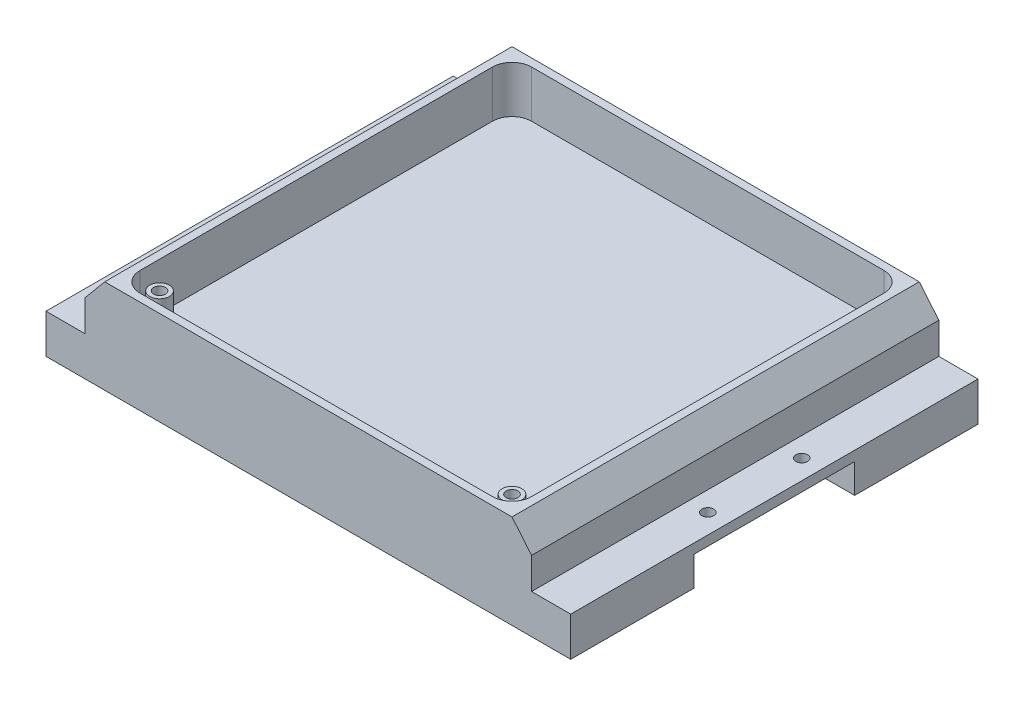
SolidWorks part; units mm, degrees
ref_plane "Front Plane" through (0, 0, 0) normal (0, 0, 1) x (1, 0, 0)
ref_plane "Top Plane" through (0, 0, 0) normal (0, 1, 0) x (1, 0, 0)
ref_plane "Right Plane" through (0, 0, 0) normal (1, 0, 0) x (0, 0, -1)
sketch "Sketch1" plane through (0, 0, 0) normal (0, 1, 0) x (1, 0, 0)
  line L5 (-46, 51) -> (46, 51)
  line L11 (-51, 46) -> (-51, -46)
  line L13 (-46, -51) -> (46, -51)
  line L14 (51, 46) -> (51, -46)
  line L15 (-51, 51) -> (51, -51) construction
  line L16 (-51, -51) -> (51, 51) construction
  arc A8 (46, -51) -> (51, -46) centre (46, -46) ccw
  arc A9 (-51, -46) -> (-46, -51) centre (-46, -46) ccw
  arc A10 (46, 51) -> (51, 46) centre (46, 46) cw
  arc A11 (-46, 51) -> (-51, 46) centre (-46, 46) ccw
  point P0 (0, 0)
  dimension "D3" = 5
  dimension "D1" = 102
  dimension "D2" = 102
extrude "Boss-Extrude3" add sketch "Sketch1" along normal blind 12
sketch "Sketch4" plane through (0, 0, 0) normal (0, -1, 0) x (-1, 0, 0)
  line L0 (-46, -51) -> (-51, -51)
  line L1 (-51, -51) -> (-51, -46)
  arc A0 (-51, -46) -> (-46, -51) centre (-46, -46) ccw
extrude "Boss-Extrude5" add sketch "Sketch4" against normal blind 12
sketch "Sketch6" plane through (0, 0, 0) normal (0, -1, 0) x (1, 0, 0)
  line L2 (-51, -46) -> (-51, -51)
  line L3 (-51, -51) -> (-46, -51)
  arc A0 (-51, -46) -> (-46, -51) centre (-46, -46) ccw
extrude "Boss-Extrude6" add sketch "Sketch6" against normal blind 12
sketch "Sketch7" plane through (0, 0, 0) normal (0, -1, 0) x (1, 0, 0)
  line L0 (-46, 51) -> (-51, 51)
  line L1 (-51, 51) -> (-51, 46)
  line L2 (46, -51) -> (51, -51)
  line L3 (51, -51) -> (51, -46)
  arc A0 (-46, 51) -> (-51, 46) centre (-46, 46) ccw
  arc A1 (46, -51) -> (51, -46) centre (46, -46) ccw
extrude "Boss-Extrude7" add sketch "Sketch7" against normal blind 12
sketch "Sketch13" plane through (0, 0, 51) normal (0, 0, 1) x (1, 0, 0)
  line L1 (-51, 12) -> (51, 12)
  line L2 (-51, 12) -> (-51, 0)
  line L3 (-51, 0) -> (51, 0)
  line L4 (51, 12) -> (51, 0)
extrude "Boss-Extrude11" add sketch "Sketch13" along normal blind 1
sketch "Sketch14" plane through (51, 0, 0) normal (1, 0, 0) x (0, 0, -1)
  line L1 (-52, 12) -> (51, 12)
  line L2 (-52, 12) -> (-52, 0)
  line L3 (-52, 0) -> (51, 0)
  line L4 (51, 12) -> (51, 0)
extrude "Boss-Extrude12" add sketch "Sketch14" along normal blind 1
sketch "Sketch15" plane through (0, 0, -51) normal (0, 0, -1) x (-1, 0, 0)
  line L1 (-52, 12) -> (51, 12)
  line L2 (-52, 12) -> (-52, 0)
  line L3 (-52, 0) -> (51, 0)
  line L4 (51, 12) -> (51, 0)
extrude "Boss-Extrude13" add sketch "Sketch15" along normal blind 1
sketch "Sketch16" plane through (-51, 0, 0) normal (-1, 0, 0) x (0, 0, 1)
  line L1 (-52, 12) -> (52, 12)
  line L2 (-52, 12) -> (-52, 0)
  line L3 (-52, 0) -> (52, 0)
  line L4 (52, 12) -> (52, 0)
extrude "Boss-Extrude14" add sketch "Sketch16" along normal blind 1
sketch "Sketch17" plane through (0, 12, 0) normal (0, 1, 0) x (1, 0, 0)
  line L1 (-52, 52) -> (52, 52)
  line L2 (-52, 52) -> (-52, -52)
  line L3 (-52, -52) -> (52, -52)
  line L4 (52, 52) -> (52, -52)
  line L5 (-52, 52) -> (52, -52) construction
  line L6 (-52, -52) -> (52, 52) construction
  line L7 (-45, 50) -> (45, 50)
  line L8 (-50, 45) -> (-50, -45)
  line L9 (-45, -50) -> (45, -50)
  line L10 (50, 45) -> (50, -45)
  line L11 (-50, 50) -> (50, -50) construction
  line L12 (-50, -50) -> (50, 50) construction
  arc A0 (45, 50) -> (50, 45) centre (45, 45) cw
  arc A1 (-45, 50) -> (-50, 45) centre (-45, 45) ccw
  arc A2 (45, -50) -> (50, -45) centre (45, -45) ccw
  arc A3 (-50, -45) -> (-45, -50) centre (-45, -45) ccw
  point P0 (0, 0)
  point P7 (0, 0)
  dimension "D3" = 5
  dimension "D1" = 100
  dimension "D2" = 100
extrude "Boss-Extrude16" add sketch "Sketch17" along normal blind 12
sketch "Sketch18" plane through (0, 12, 0) normal (0, 1, 0) x (1, 0, 0)
  circle A0 centre (45, -45) radius 1.5
  circle A1 centre (45, -45) radius 2.5
extrude "Boss-Extrude18" add sketch "Sketch18" along normal blind 10
sketch "Sketch19" plane through (0, 12, 0) normal (0, 1, 0) x (1, 0, 0)
  circle A0 centre (-45, -45) radius 1.5
  circle A1 centre (-45, -45) radius 2.5
extrude "Boss-Extrude19" add sketch "Sketch19" along normal blind 10
sketch "Sketch20" plane through (52, 0, 0) normal (1, 0, 0) x (0, 0, -1)
  line L1 (-52, 24) -> (52, 24)
  line L2 (-52, 24) -> (-52, 0)
  line L3 (-52, 0) -> (52, 0)
  line L4 (52, 24) -> (52, 0)
extrude "Boss-Extrude20" add sketch "Sketch20" along normal blind 10
sketch "Sketch21" plane through (0, 0, 52) normal (0, 0, 1) x (1, 0, 0)
  line L1 (62, 24) -> (52, 24)
  line L2 (62, 24) -> (62, 18)
  line L5 (52, 24) -> (57, 18)
  line L6 (62, 18) -> (57, 18)
  dimension "D1" = 10
extrude "Cut-Extrude2" cut sketch "Sketch21" against normal blind 104
sketch "Sketch23" plane through (-52, 0, 0) normal (-1, 0, 0) x (0, 0, 1)
  line L1 (-52, 24) -> (52, 24)
  line L2 (-52, 24) -> (-52, 0)
  line L3 (-52, 0) -> (52, 0)
  line L4 (52, 24) -> (52, 0)
extrude "Boss-Extrude21" add sketch "Sketch23" along normal blind 10
sketch "Sketch24" plane through (0, 0, 52) normal (0, 0, 1) x (1, 0, 0)
  line L1 (-62, 24) -> (-52, 24)
  line L2 (-62, 24) -> (-62, 18)
  line L5 (-52, 24) -> (-57, 18)
  line L6 (-62, 18) -> (-57, 18)
extrude "Cut-Extrude3" cut sketch "Sketch24" against normal blind 104
sketch "Sketch26" plane through (0, 0, 0) normal (0, -1, 0) x (1, 0, 0)
  line L3 (-62, 20.5) -> (-52, 20.5)
  line L4 (-62, 20.5) -> (-62, -20.5)
  line L5 (-62, -20.5) -> (-52, -20.5)
  line L6 (-52, 20.5) -> (-52, -20.5)
  line L7 (-62, 20.5) -> (-52, -20.5) construction
  line L8 (-62, -20.5) -> (-52, 20.5) construction
  line L10 (52, 20.5) -> (62, 20.5)
  line L11 (52, 20.5) -> (52, -20.5)
  line L12 (52, -20.5) -> (62, -20.5)
  line L13 (62, 20.5) -> (62, -20.5)
  line L14 (52, 20.5) -> (62, -20.5) construction
  line L15 (52, -20.5) -> (62, 20.5) construction
  dimension "D1" = 10
  dimension "D2" = 41
  dimension "D3" = 10
  dimension "D4" = 41
extrude "Cut-Extrude5" cut sketch "Sketch26" against normal blind 7.5
sketch "Sketch29" plane through (0, 18, 0) normal (0, 1, 0) x (1, 0, 0)
  line L1 (57, 52) -> (62, 52)
  line L2 (57, 52) -> (57, -52)
  line L3 (57, -52) -> (62, -52)
  line L4 (62, 52) -> (62, -52)
extrude "Cut-Extrude6" cut sketch "Sketch29" against normal blind 8
sketch "Sketch30" plane through (0, 18, 0) normal (0, 1, 0) x (1, 0, 0)
  line L1 (-62, 52) -> (-57, 52)
  line L2 (-62, 52) -> (-62, -52)
  line L3 (-62, -52) -> (-57, -52)
  line L4 (-57, 52) -> (-57, -52)
extrude "Cut-Extrude7" cut sketch "Sketch30" against normal blind 8
sketch "Sketch32" plane through (-62, 0, 0) normal (-1, 0, 0) x (0, 0, 1)
  line L0 (-52, 10) -> (-52, 0)
  line L1 (-52, 0) -> (-20.5, 0)
  line L2 (-20.5, 0) -> (-20.5, 7.5)
  line L3 (-20.5, 7.5) -> (20.5, 7.5)
  line L4 (20.5, 7.5) -> (20.5, 0)
  line L5 (20.5, 0) -> (52, 0)
  line L6 (52, 0) -> (52, 10)
  line L7 (52, 10) -> (-52, 10)
extrude "Boss-Extrude22" add sketch "Sketch32" along normal blind 5
sketch "Sketch33" plane through (-52, 0, 0) normal (-1, 0, 0) x (0, 0, 1)
  line L1 (-20.5, 7.5) -> (20.5, 7.5)
  line L2 (-20.5, 7.5) -> (-20.5, 0)
  line L3 (-20.5, 0) -> (20.5, 0)
  line L4 (20.5, 7.5) -> (20.5, 0)
extrude "Boss-Extrude23" add sketch "Sketch33" along normal blind 5
sketch "Sketch34" plane through (62, 0, 0) normal (1, 0, 0) x (0, 0, -1)
  line L0 (-52, 10) -> (-52, 0)
  line L1 (-52, 0) -> (-20.5, 0)
  line L2 (-20.5, 0) -> (-20.5, 7.5)
  line L3 (-20.5, 7.5) -> (20.5, 7.5)
  line L4 (20.5, 7.5) -> (20.5, 0)
  line L5 (20.5, 0) -> (52, 0)
  line L6 (52, 0) -> (52, 10)
  line L7 (52, 10) -> (-52, 10)
extrude "Boss-Extrude24" add sketch "Sketch34" along normal blind 5
sketch "Sketch35" plane through (52, 0, 0) normal (1, 0, 0) x (0, 0, -1)
  line L1 (-20.5, 7.5) -> (20.5, 7.5)
  line L2 (-20.5, 7.5) -> (-20.5, 0)
  line L3 (-20.5, 0) -> (20.5, 0)
  line L4 (20.5, 7.5) -> (20.5, 0)
extrude "Boss-Extrude25" add sketch "Sketch35" along normal blind 5
sketch "Sketch36" plane through (0, 7.5, 0) normal (0, -1, 0) x (1, 0, 0)
  circle A0 centre (62, 12) radius 1.5
  circle A1 centre (62, -12) radius 1.5
extrude "Cut-Extrude8" cut sketch "Sketch36" against normal blind 2.5
sketch "Sketch37" plane through (0, 7.5, 0) normal (0, -1, 0) x (1, 0, 0)
  circle A0 centre (-62, 12) radius 1.5
  circle A1 centre (-62, -12) radius 1.5
extrude "Cut-Extrude9" cut sketch "Sketch37" against normal blind 2.5
